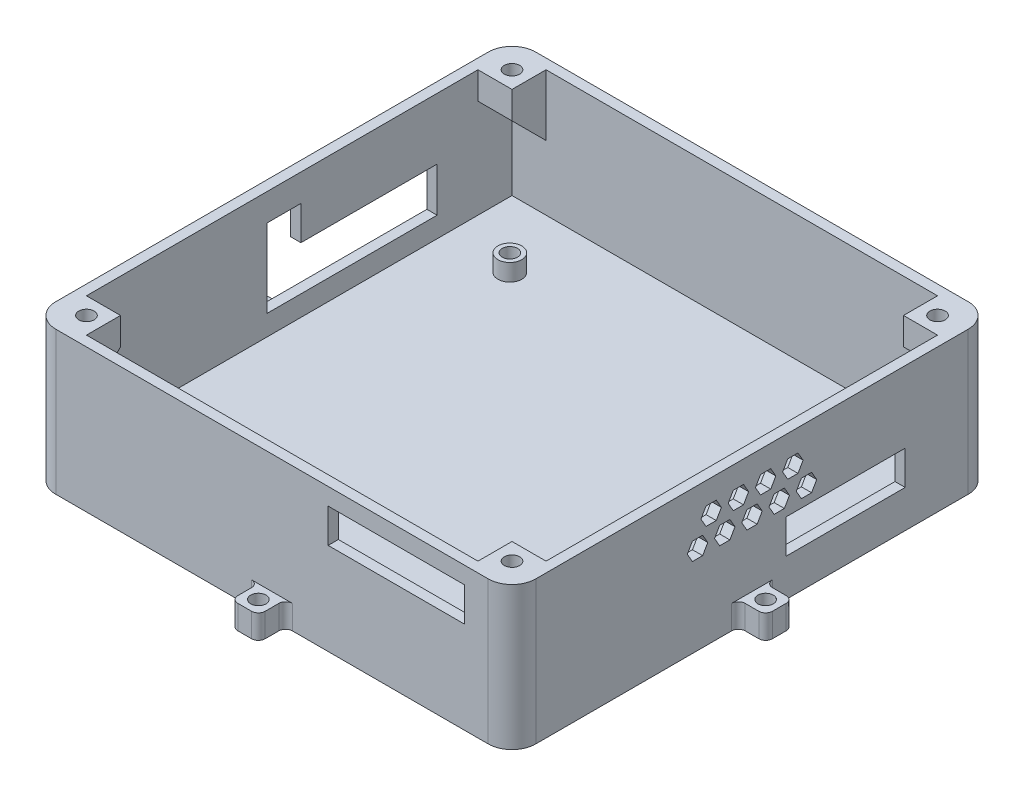
SolidWorks part; units mm, degrees
ref_plane "Front Plane" through (0, 0, 0) normal (0, 0, 1) x (1, 0, 0)
ref_plane "Top Plane" through (0, 0, 0) normal (0, 1, 0) x (1, 0, 0)
ref_plane "Right Plane" through (0, 0, 0) normal (1, 0, 0) x (0, 0, -1)
sketch "Sketch1" plane through (0, 0, 0) normal (0, 1, 0) x (1, 0, 0)
  line L0 (-48.26, 47.625) -> (48.26, 47.625) construction
  line L1 (-67.5, 67.5) -> (67.5, 67.5)
  line L2 (-67.5, 67.5) -> (-67.5, -67.5)
  line L3 (-67.5, -67.5) -> (67.5, -67.5)
  line L4 (67.5, 67.5) -> (67.5, -67.5)
  line L5 (0, -67.5) -> (0, 67.5) construction
  line L6 (-67.5, 0) -> (67.5, 0) construction
  line L7 (48.26, 47.625) -> (48.26, -47.625) construction
  circle A0 centre (-48.26, 47.625) radius 2.25
  circle A1 centre (48.26, 47.625) radius 2.25
  circle A2 centre (48.26, -47.625) radius 2.25
  circle A3 centre (-48.26, -47.625) radius 2.25
  point P0 (0, 0)
  point P12 (0, 47.625)
  point P13 (48.26, 0)
  dimension "D3" = 4.5
  dimension "D1" = 135
  dimension "D2" = 135
  dimension "D4" = 96.52
  dimension "D5" = 95.25
extrude "Boss-Extrude1" add sketch "Sketch1" along normal blind 5
sketch "Sketch2" plane through (0, 5, 0) normal (0, 1, 0) x (1, 0, 0)
  circle A0 centre (-48.26, 47.625) radius 2.25
  circle A1 centre (-48.26, 47.625) radius 3.5
  dimension "D1" = 4.5
  dimension "D2" = 7
extrude "Boss-Extrude2" add sketch "Sketch2" along normal blind 5
mirror "Mirror1" about plane through (0, 0, 0) normal (0, 0, 1) of "Boss-Extrude2"
mirror "Mirror2" about plane through (0, 0, 0) normal (1, 0, 0) of "Mirror1"
sketch "Sketch3" plane through (0, 0, 0) normal (0, -1, 0) x (1, 0, 0)
  line L0 (0, -55) -> (0, 55) construction
  line L1 (55, 0) -> (-55, 0) construction
  circle A0 centre (-48.26, 47.625) radius 3
  circle A1 centre (48.26, 47.625) radius 3
  circle A2 centre (48.26, -47.625) radius 3
  circle A3 centre (-48.26, -47.625) radius 3
  dimension "D1" = 6
extrude "Cut-Extrude1" [suppressed] cut sketch "Sketch3" against normal blind 3.5
sketch "Sketch4" plane through (0, 0, 0) normal (0, 1, 0) x (1, 0, 0)
  line L1 (-70.5, 70.5) -> (70.5, 70.5)
  line L2 (-70.5, 70.5) -> (-70.5, -70.5)
  line L3 (-70.5, -70.5) -> (70.5, -70.5)
  line L4 (70.5, 70.5) -> (70.5, -70.5)
  line L5 (0, -70.5) -> (0, 70.5) construction
  line L6 (-70.5, 0) -> (70.5, 0) construction
  line L7 (-67.5, -67.5) -> (67.5, -67.5)
  line L8 (-67.5, -67.5) -> (-67.5, 67.5)
  line L9 (-67.5, 67.5) -> (67.5, 67.5)
  line L10 (67.5, -67.5) -> (67.5, 67.5)
  line L11 (0, 67.5) -> (0, -67.5) construction
  line L12 (-67.5, 0) -> (67.5, 0) construction
  point P0 (0, 0)
  point P4 (0, 0)
  dimension "D1" = 3
  dimension "D2" = 3
extrude "Boss-Extrude3" add sketch "Sketch4" along normal blind 42
sketch "Sketch6" plane through (-70.5, 0, 0) normal (-1, 0, 0) x (0, 0, 1)
  line L1 (-45.5, 24) -> (-5.5, 24)
  line L2 (-45.5, 24) -> (-45.5, 11)
  line L3 (-45.5, 11) -> (4.5, 11)
  line L4 (4.5, 24) -> (4.5, 11)
  line L5 (-70.5, 42) -> (-70.5, 0) construction
  line L6 (-70.5, 0) -> (70.5, 0) construction
  line L9 (4.5, 24) -> (4.5, 34)
  line L10 (4.5, 34) -> (-5.5, 34)
  line L11 (-5.5, 24) -> (-5.5, 34)
  dimension "D1" = 25
  dimension "D2" = 50
  dimension "D3" = 11
  dimension "D4" = 13
  dimension "D5" = 10
  dimension "D6" = 10
extrude "Cut-Extrude2" cut sketch "Sketch6" against normal up to next
sketch "Sketch7" plane through (0, 0, 70.5) normal (0, 0, 1) x (1, 0, 0)
  line L0 (70.5, 42) -> (70.5, 0) construction
  line L1 (56.5, 27) -> (16.5, 27)
  line L2 (56.5, 27) -> (56.5, 37)
  line L3 (56.5, 37) -> (16.5, 37)
  line L4 (16.5, 27) -> (16.5, 37)
  line L5 (-70.5, 42) -> (70.5, 42) construction
  dimension "D1" = 14
  dimension "D2" = 5
  dimension "D3" = 10
  dimension "D4" = 40
extrude "Cut-Extrude3" cut sketch "Sketch7" against normal up to next
sketch "Sketch8" plane through (70.5, 0, 0) normal (1, 0, 0) x (0, 0, -1)
  line L1 (-13, 26) -> (-14.5, 28.5981)
  line L2 (-14.5, 28.5981) -> (-17.5, 28.5981)
  line L3 (-17.5, 28.5981) -> (-19, 26)
  line L4 (-19, 26) -> (-17.5, 23.4019)
  line L5 (-17.5, 23.4019) -> (-14.5, 23.4019)
  line L6 (-14.5, 23.4019) -> (-13, 26)
  line L7 (-70.5, 0) -> (70.5, 0) construction
  line L8 (-9.5, 28.5981) -> (-11, 26)
  line L9 (-6.5, 28.5981) -> (-9.5, 28.5981)
  line L10 (-6.5, 23.4019) -> (-5, 26)
  line L11 (-5, 26) -> (-6.5, 28.5981)
  line L12 (-9.5, 23.4019) -> (-6.5, 23.4019)
  line L13 (-11, 26) -> (-9.5, 23.4019)
  line L14 (-1.5, 28.5981) -> (-3, 26)
  line L15 (1.5, 28.5981) -> (-1.5, 28.5981)
  line L16 (1.5, 23.4019) -> (3, 26)
  line L17 (3, 26) -> (1.5, 28.5981)
  line L18 (-1.5, 23.4019) -> (1.5, 23.4019)
  line L19 (-3, 26) -> (-1.5, 23.4019)
  line L20 (6.5, 28.5981) -> (5, 26)
  line L21 (9.5, 28.5981) -> (6.5, 28.5981)
  line L22 (9.5, 23.4019) -> (11, 26)
  line L23 (11, 26) -> (9.5, 28.5981)
  line L24 (6.5, 23.4019) -> (9.5, 23.4019)
  line L25 (5, 26) -> (6.5, 23.4019)
  line L26 (14.5, 28.5981) -> (13, 26)
  line L27 (17.5, 28.5981) -> (14.5, 28.5981)
  line L28 (17.5, 23.4019) -> (19, 26)
  line L29 (19, 26) -> (17.5, 28.5981)
  line L30 (14.5, 23.4019) -> (17.5, 23.4019)
  line L31 (13, 26) -> (14.5, 23.4019)
  line L32 (-5.5, 35.5263) -> (-7, 32.9282)
  line L33 (-2.5, 35.5263) -> (-5.5, 35.5263)
  line L34 (-2.5, 30.3301) -> (-1, 32.9282)
  line L35 (-1, 32.9282) -> (-2.5, 35.5263)
  line L36 (-5.5, 30.3301) -> (-2.5, 30.3301)
  line L37 (-7, 32.9282) -> (-5.5, 30.3301)
  line L38 (2.5, 35.5263) -> (1, 32.9282)
  line L39 (5.5, 35.5263) -> (2.5, 35.5263)
  line L40 (5.5, 30.3301) -> (7, 32.9282)
  line L41 (7, 32.9282) -> (5.5, 35.5263)
  line L42 (2.5, 30.3301) -> (5.5, 30.3301)
  line L43 (1, 32.9282) -> (2.5, 30.3301)
  line L44 (10.5, 35.5263) -> (9, 32.9282)
  line L45 (13.5, 35.5263) -> (10.5, 35.5263)
  line L46 (13.5, 30.3301) -> (15, 32.9282)
  line L47 (15, 32.9282) -> (13.5, 35.5263)
  line L48 (10.5, 30.3301) -> (13.5, 30.3301)
  line L49 (9, 32.9282) -> (10.5, 30.3301)
  line L56 (-13.5, 35.5263) -> (-15, 32.9282)
  line L57 (-10.5, 35.5263) -> (-13.5, 35.5263)
  line L58 (-10.5, 30.3301) -> (-9, 32.9282)
  line L59 (-9, 32.9282) -> (-10.5, 35.5263)
  line L60 (-13.5, 30.3301) -> (-10.5, 30.3301)
  line L61 (-15, 32.9282) -> (-13.5, 30.3301)
  line L62 (29.1651, 22.25) -> (28.4151, 23.549) [skipped]
  line L63 (24.0849, 34.8074) -> (24.8349, 36.1064) [skipped]
  line L64 (34.5, 30.3301) -> (36, 30.3301) [skipped]
  line L65 (23.1651, 22.25) -> (23.9151, 20.951) [skipped]
  line L66 (19.5849, 37.4054) -> (18.8349, 36.1064) [skipped]
  line L67 (36, 35.5263) -> (34.5, 35.5263) [skipped]
  circle A0 centre (-16, 26) radius 2.5981 construction
  circle A1 centre (-8, 26) radius 2.5981 construction
  circle A2 centre (0, 26) radius 2.5981 construction
  circle A3 centre (8, 26) radius 2.5981 construction
  circle A4 centre (16, 26) radius 2.5981 construction
  circle A5 centre (-4, 32.9282) radius 2.5981 construction
  circle A6 centre (4, 32.9282) radius 2.5981 construction
  circle A7 centre (12, 32.9282) radius 2.5981 construction
  circle A9 centre (-12, 32.9282) radius 2.5981 construction
  arc A10 (20, 35.5263) -> (17.75, 34.2272) centre (20, 32.9282) ccw construction
  dimension "D1" = 3
  dimension "D4" = 26
  dimension "D2" = 5
  dimension "D3" = 2
extrude "Cut-Extrude4" cut sketch "Sketch8" against normal up to next
sketch "Sketch9" plane through (0, 42, 0) normal (0, 1, 0) x (1, 0, 0)
  line L1 (-67.5, 67.5) -> (-57.5, 67.5)
  line L2 (-67.5, 67.5) -> (-67.5, 57.5)
  line L3 (-67.5, 57.5) -> (-57.5, 57.5)
  line L4 (-57.5, 67.5) -> (-57.5, 57.5)
  line L5 (-55, 0) -> (55, 0) construction
  line L6 (-67.5, -67.5) -> (-57.5, -67.5)
  line L7 (-57.5, -67.5) -> (-57.5, -57.5)
  line L8 (-67.5, -67.5) -> (-67.5, -57.5)
  line L9 (-67.5, -57.5) -> (-57.5, -57.5)
  line L10 (0, -55) -> (0, 55) construction
  line L11 (67.5, 67.5) -> (57.5, 67.5)
  line L12 (67.5, 57.5) -> (57.5, 57.5)
  line L13 (57.5, 67.5) -> (57.5, 57.5)
  line L14 (67.5, 67.5) -> (67.5, 57.5)
  line L15 (67.5, -67.5) -> (67.5, -57.5)
  line L16 (67.5, -67.5) -> (57.5, -67.5)
  line L17 (57.5, -67.5) -> (57.5, -57.5)
  line L18 (67.5, -57.5) -> (57.5, -57.5)
  circle A0 centre (-62.5, 62.5) radius 2.25
  circle A1 centre (-62.5, -62.5) radius 2.25
  circle A2 centre (62.5, 62.5) radius 2.25
  circle A3 centre (62.5, -62.5) radius 2.25
  point P8 (-62.5, 57.5)
  point P11 (-57.5, 62.5)
  dimension "D3" = 4.5
  dimension "D1" = 10
  dimension "D2" = 10
extrude "Boss-Extrude4" add sketch "Sketch9" against normal blind 8
chamfer "Chamfer2" distance 10 angle 45 4 edges at (-62.5, 34, -67.5) (-62.5, 34, 67.5) (62.5, 34, 67.5) (62.5, 34, -67.5)
sketch "Sketch10" plane through (0, 0, 70.5) normal (0, 0, 1) x (1, 0, 0)
  line L0 (-70.5, 0) -> (70.5, 0) construction
  line L1 (-4, 0) -> (4, 0)
  line L2 (-4, 0) -> (-4, 7)
  line L3 (-4, 7) -> (4, 7)
  line L4 (4, 0) -> (4, 7)
  point P6 (0, 7)
  dimension "D1" = 8
  dimension "D2" = 7
extrude "Boss-Extrude5" add sketch "Sketch10" along normal blind 8
sketch "Sketch11" plane through (0, 7, 0) normal (0, 1, 0) x (1, 0, 0)
  line L0 (4, -78.5) -> (-4, -78.5) construction
  line L1 (4, -78.5) -> (4, -70.5) construction
  circle A0 centre (0, -74.5) radius 2.25
  point P5 (0, -78.5)
  point P10 (4, -74.5)
  dimension "D1" = 4.5
extrude "Cut-Extrude5" cut sketch "Sketch11" against normal through all
pattern_circular "CirPattern1" count 4 over 360 about axis through (0, 5, 0) along (0, 1, 0) of "Boss-Extrude5", "Cut-Extrude5"
fillet "Fillet1" radius 2 16 edges at (-4, 3.5, 70.5) (-4, 3.5, 78.5) (4, 3.5, 78.5) (4, 3.5, 70.5) (-78.5, 3.5, 4) (-70.5, 3.5, 4) (-78.5, 3.5, -4) (-70.5, 3.5, -4) (-4, 3.5, -70.5) (-4, 3.5, -78.5) (4, 3.5, -78.5) (4, 3.5, -70.5) (70.5, 3.5, -4) (78.5, 3.5, -4) (78.5, 3.5, 4) (70.5, 3.5, 4)
sketch "Sketch12" plane through (70.5, 0, 0) normal (1, 0, 0) x (0, 0, -1)
  line L0 (70.5, 42) -> (70.5, 0) construction
  line L1 (10, 21) -> (45, 21)
  line L2 (10, 21) -> (10, 11)
  line L3 (10, 11) -> (45, 11)
  line L4 (45, 21) -> (45, 11)
  line L5 (6, 0) -> (70.5, 0) construction
  dimension "D1" = 10
  dimension "D2" = 35
  dimension "D3" = 25.5
  dimension "D4" = 11
extrude "Cut-Extrude6" cut sketch "Sketch12" against normal up to next
fillet "Fillet2" radius 7 4 edges at (-70.5, 21, -70.5) (70.5, 21, -70.5) (70.5, 21, 70.5) (-70.5, 21, 70.5)
